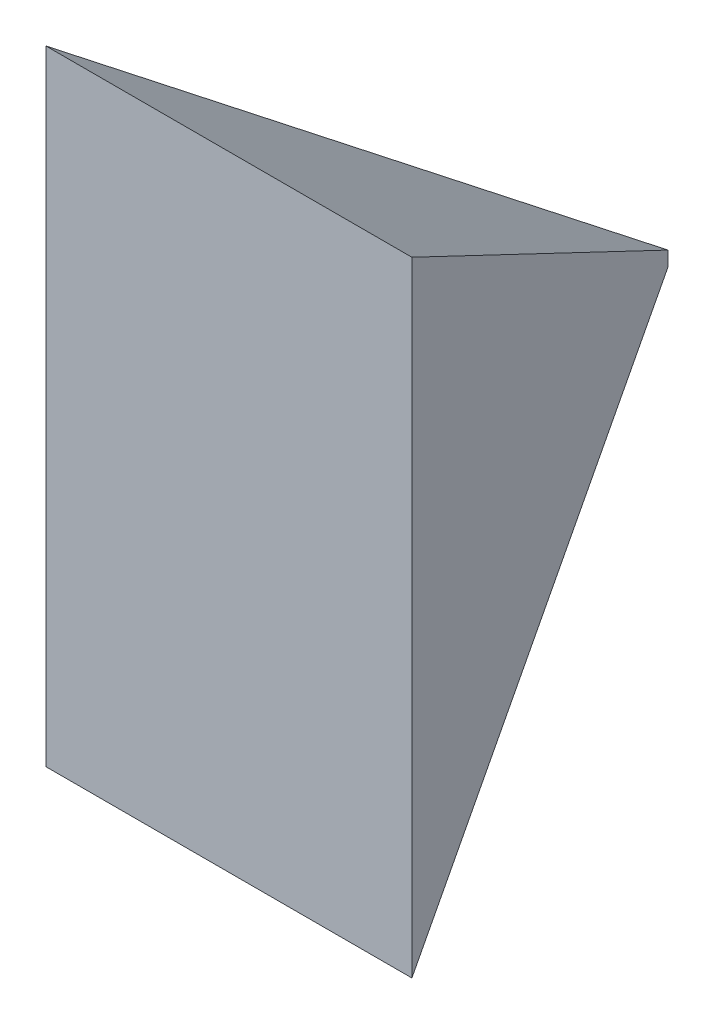
SolidWorks part; units mm, degrees
ref_plane "Front Plane" through (0, 0, 0) normal (0, 0, 1) x (1, 0, 0)
ref_plane "Top Plane" through (0, 0, 0) normal (0, 1, 0) x (1, 0, 0)
ref_plane "Right Plane" through (0, 0, 0) normal (1, 0, 0) x (0, 0, -1)
sketch "Sketch3" plane through (0, 0, 47.65) normal (0, 1, 0) x (1, 0, 0)
  line L0 (-12.5, 47.65) -> (0, 77.65)
  line L1 (0, 77.65) -> (12.5, 47.65)
  line L2 (12.5, 47.65) -> (-12.5, 47.65)
  point P6 (0, 47.65)
  dimension "D1" = 30
  dimension "D2" = 0
  dimension "D3" = 32.5
extrude "Boss-Extrude1" add sketch "Sketch3" along normal blind 42.65
sketch "Sketch4" plane through (0, 0, -4.2308) normal (1, 0, 0) x (0, 0, -1)
  line L0 (-4.2308, 42.65) -> (25.7692, 21.825)
  line L1 (25.7692, 42.65) -> (25.7692, 0) construction
  line L2 (25.7692, 21.825) -> (25.7692, 42.65)
  line L3 (-4.2308, 42.65) -> (25.7692, 42.65) construction
  line L4 (25.7692, 42.65) -> (-4.2308, 42.65)
  line L5 (-4.2308, 0) -> (25.7692, 0)
  line L6 (25.7692, 0) -> (25.7692, 20.825)
  line L7 (25.7692, 20.825) -> (-4.2308, 0)
  line L9 (-4.2308, 42.65) -> (-4.2308, 0) construction
  point P17 (-4.2308, 21.325)
  dimension "D1" = 1
  dimension "D2" = 0.5
extrude "Cut-Extrude1" cut sketch "Sketch4" against normal through all both and the other way through all
ref_plane "B Mid Plane" through (0, 21.325, 0) normal (0, -1, 0) x (-1, 0, 0)
